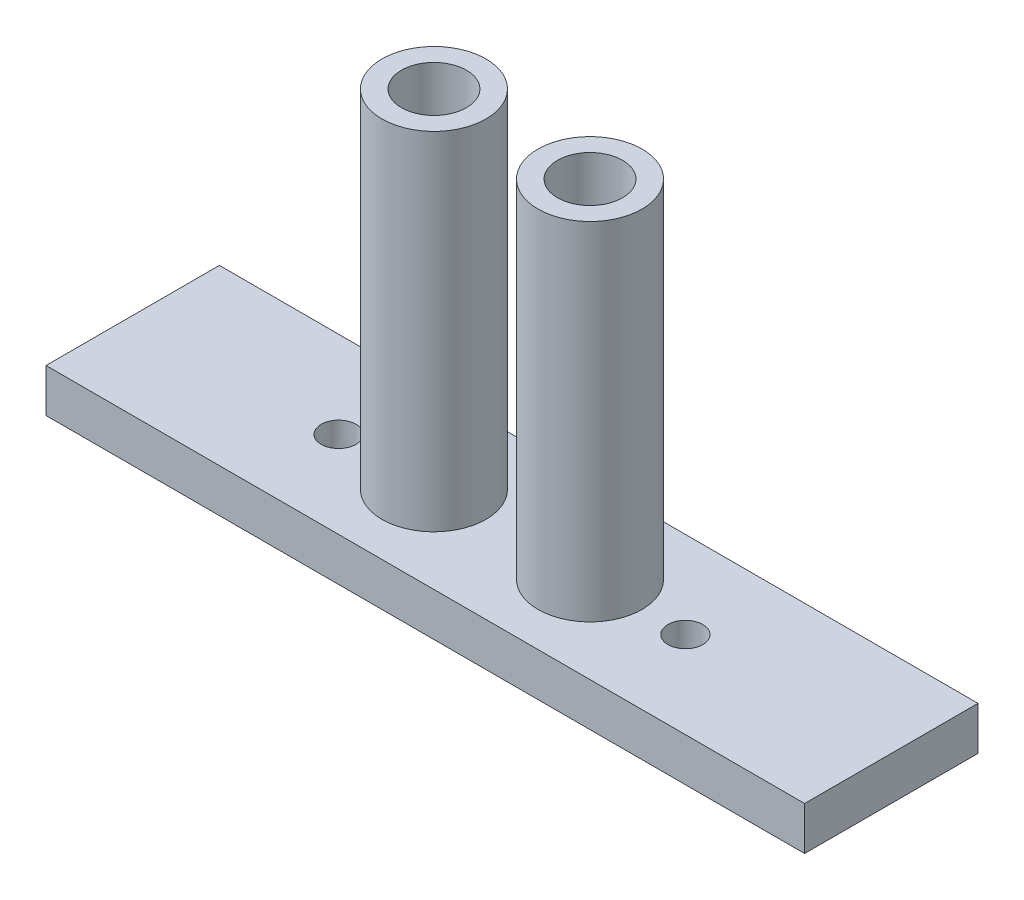
SolidWorks part; units mm, degrees
ref_plane "Front Plane" through (0, 0, 0) normal (0, 0, 1) x (1, 0, 0)
ref_plane "Top Plane" through (0, 0, 0) normal (0, 1, 0) x (1, 0, 0)
ref_plane "Right Plane" through (0, 0, 0) normal (1, 0, 0) x (0, 0, -1)
sketch "Sketch1" plane through (0, 0, 0) normal (0, 1, 0) x (1, 0, 0)
  line L1 (0, 0) -> (-111.125, 0)
  line L2 (0, 0) -> (0, -25.4)
  line L3 (0, -25.4) -> (-111.125, -25.4)
  line L4 (-111.125, 0) -> (-111.125, -25.4)
  dimension "D1" = 111.125
  dimension "D2" = 25.4
extrude "Boss-Extrude1" add sketch "Sketch1" along normal blind 6.35 contours L2 L1 L4 L3
sketch "Sketch2" plane through (0, 6.35, 0) normal (0, 1, 0) x (1, 0, 0)
  line L1 (0, 0) -> (0, -25.4) construction
  line L3 (0, -25.4) -> (-111.125, -25.4) construction
  line L4 (0, 0) -> (-111.125, 0) construction
  circle A1 centre (-30.1625, -12.7) radius 2.5527
  circle A2 centre (-80.9625, -12.7) radius 2.5527
  circle A3 centre (-66.9925, -12.7) radius 9.525 construction
  circle A4 centre (-44.1325, -12.7) radius 9.525 construction
  circle A5 centre (-44.1325, -12.7) radius 7.62
  circle A6 centre (-66.9925, -12.7) radius 7.62
  circle A8 centre (-44.1325, -12.7) radius 4.7625
  circle A9 centre (-66.9925, -12.7) radius 4.7625
  point P10 (0, 0)
  point P16 (0, 0)
  point P17 (-55.5625, -25.4)
  point P23 (0, -12.7)
  dimension "D1" = 15.24
  dimension "D3" = 12.7
  dimension "D2" = 15.24
  dimension "D4" = 12.7
  dimension "D5" = 11.43
  dimension "D6" = 11.43
extrude "Boss-Extrude2" add sketch "Sketch2" along normal blind 50.8 contours A8 | A5 | A9 | A6
extrude "Cut-Extrude1" cut sketch "Sketch2<9>" against normal through all contours A1 | A2
sketch "Sketch2<9>" plane through (0, 6.35, 0) normal (0, 1, 0) x (1, 0, 0) same geometry as "Sketch2"
